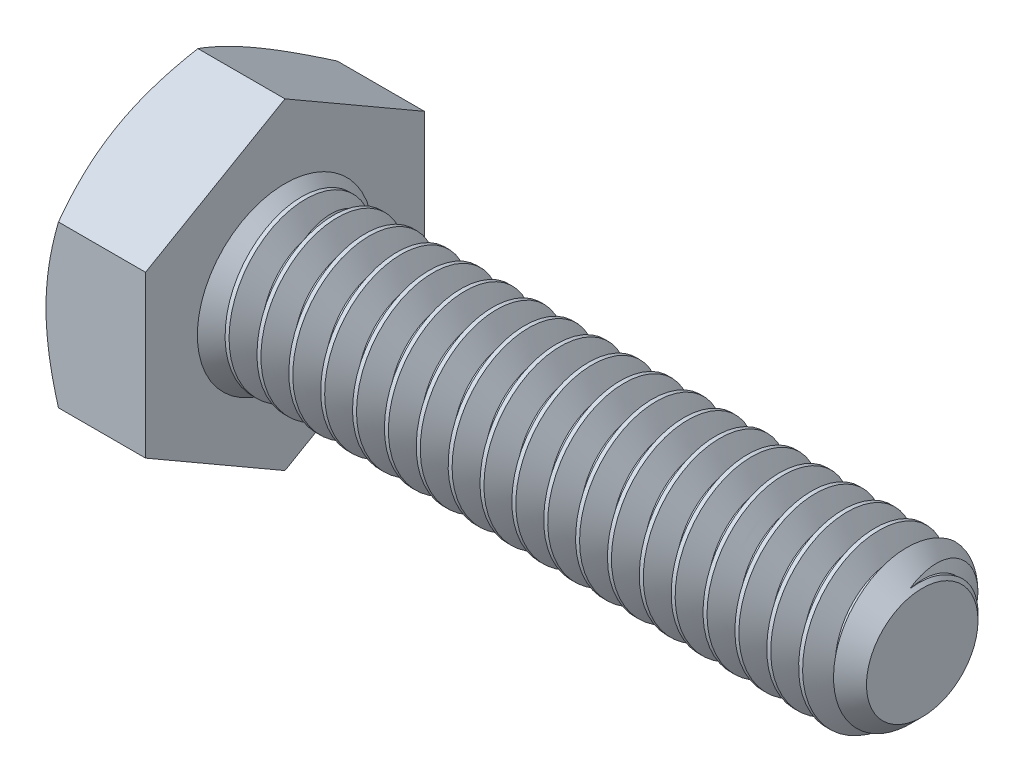
SolidWorks part; units mm, degrees
ref_plane "Front Plane" through (0, 0, 0) normal (0, 0, 1) x (1, 0, 0)
ref_plane "Top Plane" through (0, 0, 0) normal (0, 1, 0) x (1, 0, 0)
ref_plane "Right Plane" through (0, 0, 0) normal (1, 0, 0) x (0, 0, -1)
sketch "Sketch1" plane through (0, 0, 0) normal (0, 0, 1) x (1, 0, 0)
  line L0 (-14.6844, 0) -> (14.6844, 0) construction
  line L1 (14.6844, 3.175) -> (14.6844, -3.175) construction
  line L2 (-10.7156, 5.5562) -> (-10.7156, -5.5562) construction
  line L3 (-14.6844, 5.5562) -> (-14.6844, -5.5562) construction
  line L4 (15.875, -3.3125) -> (15.24, -2.2126) construction
  line L5 (15.24, -2.2126) -> (14.605, -3.3125) construction
  line L6 (14.605, -3.3125) -> (15.875, -3.3125) construction
  line L7 (15.7956, -3.175) -> (14.6844, -3.175) construction
  line L8 (15.24, -3.3125) -> (15.24, -3.175) construction
  line L9 (15.24, -3.175) -> (15.24, -2.3501) construction
  line L10 (15.24, -2.3501) -> (15.24, -2.2126) construction
  line L15 (15.3194, -2.3501) -> (15.1606, -2.3501)
  line L16 (15.8353, -3.2437) -> (14.6447, -3.2437)
  line L17 (15.1606, -2.3501) -> (14.6447, -3.2437)
  line L18 (15.3194, -2.3501) -> (15.8353, -3.2437)
  point P9 (-10.7156, 0)
  point P10 (9.7455, -3.175)
  point P24 (15.24, -3.2437)
  dimension "Head Ht" = 3.9688
  dimension "D1" = 4.9389
  dimension "Pitch" = 1.27
  dimension "D3" = 0.1588
  dimension "Head Width" = 11.1125
  dimension "Length" = 25.4
  dimension "Screw Size" = 6.35
ref_plane "Plane2" through (14.6844, 0, 0) normal (1, 0, 0) x (0, 0, -1)
sketch "Sketch5" plane through (14.6844, 0, 0) normal (1, 0, 0) x (0, 0, -1)
  circle A0 centre (0, 0) radius 3.175
extrude "Boss-Extrude3" add sketch "Sketch5" against normal up to vertex (25.4 mm away) up to point (-10.7156, 0, 0)
chamfer "Chamfer1" distance 0.9525 angle 45 1 edges at (14.6844, 0, -3.175)
sketch "Sketch6" plane through (-10.7156, 0, 0) normal (-1, 0, 0) x (0, 0, 1)
  line L0 (0, 5.5562) -> (0, -5.5562) construction
  line L1 (5.5562, 3.2079) -> (0, 6.4158)
  line L2 (0, 6.4158) -> (-5.5563, 3.2079)
  line L3 (-5.5563, 3.2079) -> (-5.5562, -3.2079)
  line L4 (-5.5562, -3.2079) -> (0, -6.4158)
  line L5 (0, -6.4158) -> (5.5563, -3.2079)
  line L6 (5.5563, -3.2079) -> (5.5562, 3.2079)
  circle A0 centre (0, 0) radius 5.5562 construction
extrude "Boss-Extrude4" add sketch "Sketch6" along normal up to vertex (3.9688 mm away) up to point (-14.6844, -5.5562, 0)
sketch "Sketch7" plane through (-14.6844, 0, 0) normal (-1, 0, 0) x (0, 0, 1)
  circle A0 centre (0, 0) radius 5.5562 construction
  circle A1 centre (0, 0) radius 5.5562
sketch "Sketch8" plane through (-14.6844, 0, 0) normal (-1, 0, 0) x (0, 0, 1)
  circle A0 centre (0, 0) radius 5.5562 construction
  circle A1 centre (0, 0) radius 5.5562
extrude "Cut-Extrude3" cut sketch "Sketch8" against normal through all draft 60 flip side to cut
split "Split1" bodies to split 113 resulting bodies 118 119 split by face at (-10.7156, 0, 3.175)
sketch "Sketch9" plane through (14.6844, 0, 0) normal (1, 0, 0) x (0, 0, -1)
  circle A0 centre (0, 0) radius 3.175 construction
  circle A1 centre (0, 0) radius 3.175
curve "Helix/Spiral1" pitch 1.27 height 26.67 radius 3.175 centre (14.6844, 0, 0) axis (-1, 0, 0) start towards (0, 0, -1)
sketch "Sketch10" plane through (0, 0, 0) normal (0, 0, 1) x (1, 0, 0)
  line L8 (15.3194, -2.3501) -> (15.1606, -2.3501) construction
  line L9 (15.1606, -2.3501) -> (14.6447, -3.2437) construction
  line L10 (15.8353, -3.2437) -> (14.6447, -3.2437) construction
  line L11 (15.3194, -2.3501) -> (15.8353, -3.2437) construction
  line L12 (15.3194, -2.3501) -> (15.1606, -2.3501)
  line L13 (15.1606, -2.3501) -> (14.6447, -3.2437)
  line L14 (15.8353, -3.2437) -> (14.6447, -3.2437)
  line L15 (15.3194, -2.3501) -> (15.8353, -3.2437)
sweep "Cut-Sweep1" cut profiles "Sketch10" path "Helix/Spiral1" align with end faces yes
combine bodies "Combine1" operation type add bodies to combine 119 120
sketch "Sketch11" plane through (-10.7156, 0, 0) normal (1, 0, 0) x (0, 0, -1)
  line L0 (0, 5.5562) -> (0, -5.5562) construction
  circle A0 centre (0, 0) radius 3.4925
  point P3 (0, -3.4925)
  dimension "D1" = 0.3175
extrude "Boss-Extrude5" add sketch "Sketch11" along normal through all draft 45
equation "\"D3@Helix/Spiral1\"= \"Length@Sketch1\" + \"Pitch@Sketch1\""
equation "\"D1@Chamfer1\" = \"Pitch@Sketch1\" * .75"
equation "\"D4@Helix/Spiral1\"=\"Pitch@Sketch1\""
equation "\"D3@Sketch1\" = \"Pitch@Sketch1\" / 8"
equation "\"D1@Sketch11\"=\"Pitch@Sketch1\"/4"
